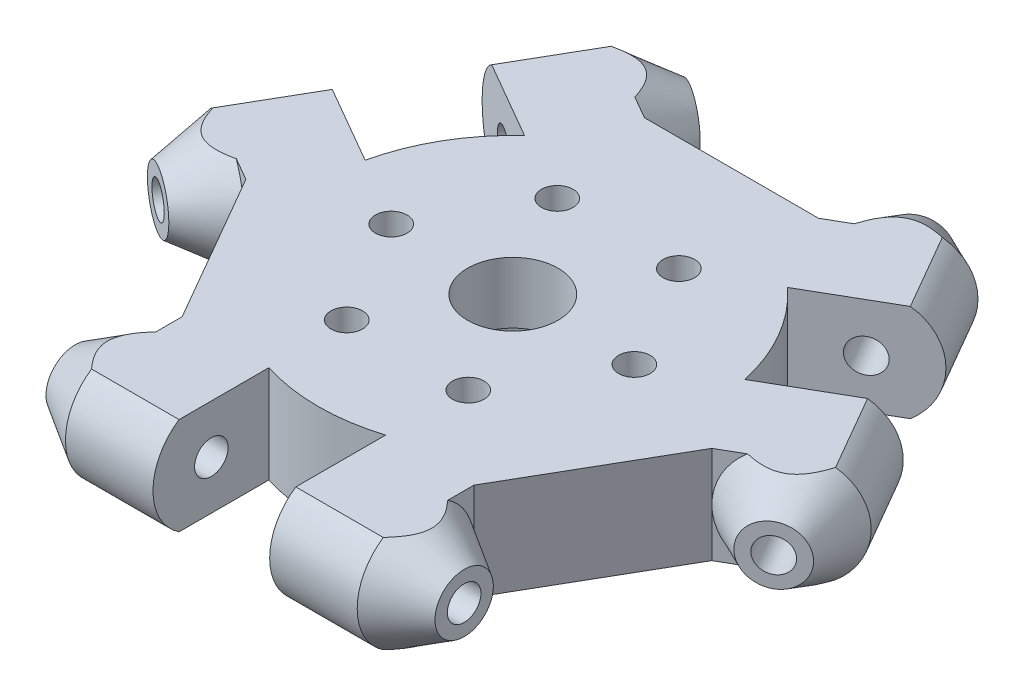
SolidWorks part; units mm, degrees
material "ABS"
ref_plane "Front Plane" through (0, 0, 0) normal (0, 0, 1) x (1, 0, 0)
ref_plane "Top Plane" through (0, 0, 0) normal (0, 1, 0) x (1, 0, 0)
ref_plane "Right Plane" through (0, 0, 0) normal (1, 0, 0) x (0, 0, -1)
sketch "Sketch4" plane through (0, 0, 0) normal (0, 1, 0) x (1, 0, 0)
  line L4 (23.8468, 20.6962) -> (13.5227, 14.7355)
  line L17 (23.8468, 20.6962) -> (19.3468, 28.4904)
  line L18 (19.3468, 28.4904) -> (8.9545, 22.4904)
  line L19 (8.9545, 22.4904) -> (-8.9545, 22.4904)
  line L28 (0, 0) -> (0, 20) construction
  line L29 (0, 0) -> (17.3205, 10) construction
  line L30 (14.1506, 25.4904) -> (30.9357, -3.5822) construction
  line L31 (-23.8468, 20.6962) -> (-13.5227, 14.7355)
  line L32 (-23.8468, 20.6962) -> (-19.3468, 28.4904)
  line L33 (-19.3468, 28.4904) -> (-8.9545, 22.4904)
  line L34 (29.8468, 10.3038) -> (19.5227, 4.3432)
  line L35 (29.8468, 10.3038) -> (34.3468, 2.5096)
  line L36 (34.3468, 2.5096) -> (23.9545, -3.4904)
  line L37 (15, -19) -> (23.9545, -3.4904)
  line L38 (15, -31) -> (15, -19)
  line L39 (6, -31) -> (15, -31)
  line L40 (6, -31) -> (6, -19.0788)
  line L41 (-6, -31) -> (-6, -19.0788)
  line L42 (-6, -31) -> (-15, -31)
  line L43 (-15, -31) -> (-15, -19)
  line L44 (-23.9545, -3.4904) -> (-15, -19)
  line L45 (-34.3468, 2.5096) -> (-23.9545, -3.4904)
  line L46 (-29.8468, 10.3038) -> (-34.3468, 2.5096)
  line L47 (-29.8468, 10.3038) -> (-19.5227, 4.3432)
  arc A0 (-13.5227, 14.7355) -> (-19.5227, 4.3432) centre (0, 0) ccw
  arc A1 (19.5227, 4.3432) -> (13.5227, 14.7355) centre (0, 0) ccw
  arc A2 (-6, -19.0788) -> (6, -19.0788) centre (0, 0) ccw
  circle A9 centre (0, 0) radius 22.4904 construction
  point P67 (0, 0)
  dimension "D2" = 20
  dimension "D8" = 60
  dimension "D12" = 9
  dimension "D13" = 25
  dimension "D14" = 12
  dimension "D9" = 15
  dimension "D15" = 3
extrude "Boss-Extrude1" add sketch "Sketch4" along normal blind 5 and the other way blind 5
sketch "Sketch6" plane through (0, 0, 0) normal (0, 1, 0) x (1, 0, 0)
  line L0 (-15, -25) -> (15, -25) construction
  line L1 (-15, -19) -> (-15, -31) construction
  line L2 (15, -31) -> (15, -19) construction
  line L3 (-15, -25) -> (-20, -25)
  line L4 (-20, -25) -> (-20, -28)
  line L5 (-20, -28) -> (-15, -31)
  line L6 (-15, -31) -> (-15, -25)
  line L7 (0, 0) -> (0, -25) construction
  line L8 (15, -31) -> (15, -25)
  line L9 (20, -28) -> (15, -31)
  line L10 (20, -25) -> (20, -28)
  line L11 (15, -25) -> (20, -25)
  dimension "D1" = 25
  dimension "D2" = 5
  dimension "D3" = 3
revolve "Revolve1" add sketch "Sketch6" angle 360 about L0
pattern_circular "CirPattern1" count 3 over 360 about axis through (0, 5, 0) along (0, 1, 0) of "Revolve1"
sketch "Sketch7" plane through (0, 0, 0) normal (1, 0, 0) x (0, 0, -1)
  line L0 (-28.3166, 5) -> (-19, 5)
  line L1 (-19, 5) -> (-19, 25)
  line L2 (-19, 25) -> (-39, 25)
  line L3 (-39, 25) -> (-39, -25)
  line L4 (-39, -25) -> (-19, -25)
  line L5 (-19, -25) -> (-19, -5)
  line L6 (-19, -5) -> (-28.3166, -5)
  circle A0 centre (-25, 0) radius 1.725
  arc A1 (-28.3166, 5) -> (-28.3166, -5) centre (-25, 0) ccw
  arc A2 (-21.6834, 5) -> (-28.3166, 5) centre (-25, 0) ccw construction
  dimension "D1" = 3.45
  dimension "D2" = 20
  dimension "D3" = 20
  dimension "D4" = 20
extrude "Cut-Extrude2" cut sketch "Sketch7" against normal through all and the other way through all
pattern_circular "CirPattern2" count 3 over 360 about axis through (0, 5, 0) along (0, 1, 0) of "Cut-Extrude2"
sketch "Sketch8" plane through (0, 0, 0) normal (0, 1, 0) x (1, 0, 0)
  circle A0 centre (0, 0) radius 8.5
  circle A1 centre (-12.5, 0) radius 1.625
  circle A2 centre (0, 0) radius 12.5 construction
  circle A3 centre (-6.25, 10.8253) radius 1.625
  circle A4 centre (6.25, 10.8253) radius 1.625
  circle A5 centre (12.5, 0) radius 1.625
  circle A6 centre (6.25, -10.8253) radius 1.625
  circle A7 centre (-6.25, -10.8253) radius 1.625
  point P18 (0, 0)
  dimension "D1" = 17
  dimension "D2" = 3.25
  dimension "D3" = 25
  dimension "D4" = 6
extrude "Cut-Extrude3" cut sketch "Sketch8" against normal through all and the other way through all
sketch "Sketch9" plane through (0, 5, 0) normal (0, 1, 0) x (1, 0, 0)
  circle A0 centre (0, 0) radius 8.5
  circle A1 centre (0, 0) radius 4.65
  circle A2 centre (0, 0) radius 8.5 construction
  dimension "D1" = 9.3
extrude "Boss-Extrude2" add sketch "Sketch9" against normal blind 6.3
